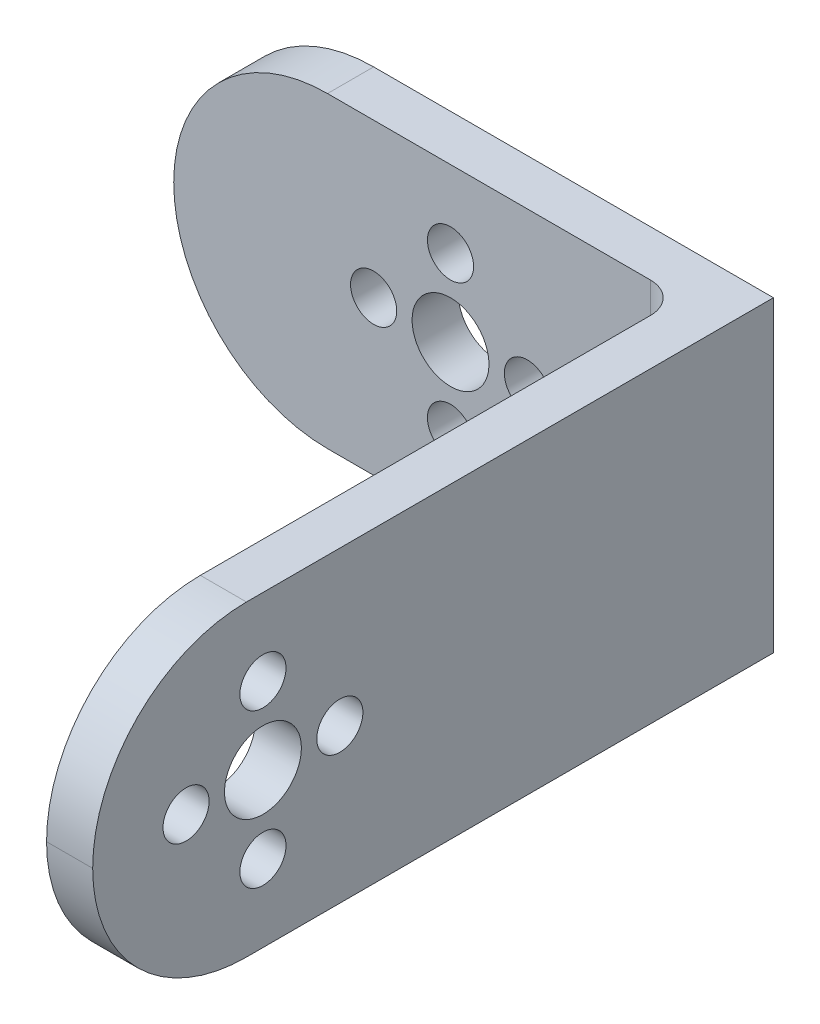
SolidWorks part; units mm, degrees
ref_plane "Plan de face" through (0, 0, 0) normal (0, 0, 1) x (1, 0, 0)
ref_plane "Plan de dessus" through (0, 0, 0) normal (0, 1, 0) x (1, 0, 0)
ref_plane "Plan de droite" through (0, 0, 0) normal (1, 0, 0) x (0, 0, -1)
sketch "Esquisse1" plane through (0, 0, 0) normal (0, 0, 1) x (1, 0, 0)
  line L0 (3, 20) -> (3, 0)
  line L1 (0, 0) -> (36, 0)
  line L2 (0, 0) -> (0, 20)
  line L3 (0, 20) -> (36, 20)
  line L4 (36, 0) -> (36, 20)
  line L5 (33, 20) -> (33, 0)
  dimension "D1" = 36
  dimension "D2" = 3
  dimension "20" = 20
  dimension "D3" = 3
extrude "Boss.-Extru.1" add sketch "Esquisse1" along normal blind 41.27 contours L3 L5 L1 L4 region at (34.5, 10, 0)
extrude "Boss.-Extru.2" add sketch "Esquisse1<3>" against normal blind 3 contours L3 L4 L1 L2
sketch "Esquisse1<3>" plane through (0, 0, 0) normal (0, 0, 1) x (1, 0, 0) same geometry as "Esquisse1"
sketch "Esquisse3" plane through (36, 0, 0) normal (1, 0, 0) x (0, 0, -1)
  line L0 (-41.27, 10) -> (3, 10) construction
  line L1 (-41.27, 0) -> (-41.27, 20) construction
  line L2 (3, 0) -> (3, 20) construction
  line L8 (-30.1979, 10) -> (-30.1979, 18.5318) construction
  line L9 (-30.1979, 10) -> (-30.1979, 1.2804) construction
  circle A1 centre (-30.1979, 10) radius 2.5
  circle A2 centre (-30.1979, 15) radius 1.5
  circle A3 centre (-30.1979, 5) radius 1.5
  circle A4 centre (-25.1979, 10) radius 1.5
  circle A5 centre (-30.1979, 5) radius 1.5
  circle A6 centre (-35.1979, 10) radius 1.5
  dimension "D1" = 11.0721
  dimension "D2" = 5
  dimension "D3" = 3
  dimension "D4" = 3
  dimension "D5" = 5
  dimension "D6" = 5
  dimension "D7" = 4
extrude "Enlèv. mat.-Extru.2" cut sketch "Esquisse3" against normal blind 85 contours A2 | A3 | A6 | A4 | A1 region at (36, 15, 30.1979) region at (36, 5, 30.1979) region at (36, 10, 25.1979) region at (36, 10, 35.1979)
fillet "Congé2" radius 2 1 edges at (33, 10, 0)
sketch "Esquisse6" plane through (0, 0, 0) normal (0, -1, 0) x (-1, 0, 0)
  line L0 (-33, -2) -> (-36, -2) construction
  line L1 (-36, 3) -> (-36, -41.27) construction
sketch "Esquisse7" plane through (0, 0, -3) normal (0, 0, -1) x (-1, 0, 0)
  line L0 (-36, 10) -> (0, 10) construction
  line L1 (-36, 0) -> (-36, 20) construction
  line L2 (0, 0) -> (0, 20) construction
  line L3 (-18, 10) -> (-18, 8.6257) construction
  line L4 (-18, 10) -> (-18, -8.6257) construction
  circle A3 centre (-18, 10) radius 2.5
  circle A4 centre (-18, 15) radius 1.5
  circle A5 centre (-18, 5) radius 1.5
  circle A10 centre (-13, 10) radius 1.5
  circle A11 centre (-18, 5) radius 1.5
  circle A12 centre (-23, 10) radius 1.5
  point P6 (-18, 10)
  dimension "D1" = 5
  dimension "D2" = 3
  dimension "D3" = 3
  dimension "D4" = 5
  dimension "D5" = 5
  dimension "D6" = 4
fillet "Congé3" radius 10 4 edges at (0, 20, -1.5) (0, 0, -1.5) (34.5, 20, 41.27) (34.5, 0, 41.27)
extrude "Enlèv. mat.-Extru.3" cut sketch "Esquisse7" against normal blind 10 contours A12 | A4 | A10 | A5 | A3 region at (18, 15, -3) region at (18, 5, -3) region at (13, 10, -3) region at (23, 10, -3)
